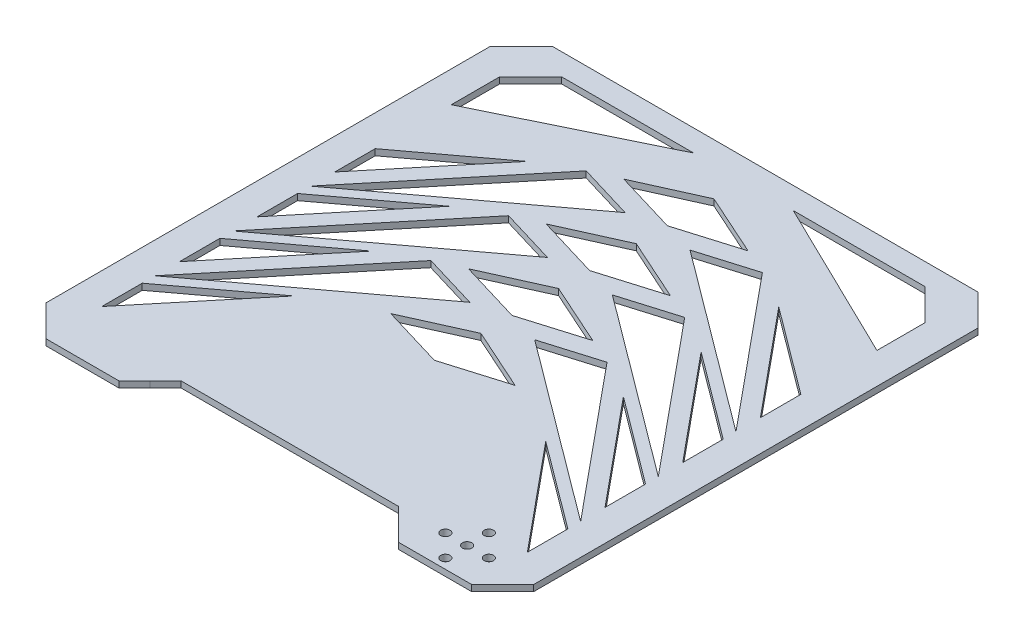
SolidWorks part; units mm, degrees
material "PE 低密度结膜"
ref_plane "前视基准面" through (0, 0, 0) normal (0, 0, 1) x (1, 0, 0)
ref_plane "上视基准面" through (0, 0, 0) normal (0, 1, 0) x (1, 0, 0)
ref_plane "右视基准面" through (0, 0, 0) normal (1, 0, 0) x (0, 0, -1)
sketch "草图1" plane through (0, 0, 0) normal (0, 1, 0) x (1, 0, 0)
  line L1 (-78.5, 81.5) -> (78.5, 81.5)
  line L2 (-78.5, 81.5) -> (-78.5, -81.5)
  line L3 (-78.5, -81.5) -> (78.5, -81.5)
  line L4 (78.5, 81.5) -> (78.5, -81.5)
  line L5 (-78.5, 81.5) -> (78.5, -81.5) construction
  line L6 (-78.5, -81.5) -> (78.5, 81.5) construction
  point P0 (0, 0)
  dimension "D1" = 163
  dimension "D2" = 157
extrude "凸台-拉伸1" add sketch "草图1" along normal blind 2
sketch "草图2" plane through (0, 0, 0) normal (0, -1, 0) x (-1, 0, 0)
  circle A0 centre (-56.9012, -78.3444) radius 1.5
  circle A1 centre (-63.9012, -71.3444) radius 1.5
  circle A2 centre (-56.9012, -64.3444) radius 1.5
  circle A3 centre (-49.9012, -71.3444) radius 1.5
  circle A4 centre (-56.9012, -71.3444) radius 1.5
  dimension "D1" = 3
  dimension "D2" = 3
  dimension "D3" = 3
  dimension "D4" = 3
extrude "切除-拉伸1" cut sketch "草图2" against normal blind 10
chamfer "Chamfer1" distance 10 angle 45 1 edges at (-78.5, 1, -81.5)
chamfer "Chamfer2" distance 10 angle 45 2 edges at (78.5, 1, 81.5) (-78.5, 1, 81.5)
chamfer "Chamfer3" distance 10 angle 45 1 edges at (78.5, 1, -81.5)
sketch "Sketch1" plane through (0, 2, 0) normal (0, 1, 0) x (1, 0, 0)
  line L0 (0, 0) -> (20, 6)
  line L1 (20, 6) -> (0, 15)
  line L2 (0, 15) -> (-20, 6)
  line L3 (-20, 6) -> (0, 0)
  line L4 (28.3522, 2.2415) -> (10.4403, -3.1321)
  line L5 (10.4403, -3.1321) -> (68.5, -46.4073)
  line L6 (68.5, -46.4073) -> (28.3522, 2.2415)
  line L7 (78.5, -71.5) -> (78.5, 71.5) construction
  line L8 (0, 81.5) -> (0, -81.5) construction
  line L9 (68.5, 81.5) -> (-68.5, 81.5) construction
  line L10 (-68.5, -81.5) -> (68.5, -81.5) construction
  line L11 (-68.5, -46.4073) -> (-28.3522, 2.2415)
  line L12 (-10.4403, -3.1321) -> (-68.5, -46.4073)
  line L13 (-28.3522, 2.2415) -> (-10.4403, -3.1321)
  line L17 (40.5567, -4.6917) -> (68.5, -25.5195)
  line L18 (68.5, -25.5195) -> (68.5, -38.5518)
  line L19 (40.5567, -4.6917) -> (68.5, -38.5518)
  line L20 (-68.5, -25.5195) -> (-68.5, -38.5518)
  line L21 (-40.5567, -4.6917) -> (-68.5, -38.5518)
  line L22 (-40.5567, -4.6917) -> (-68.5, -25.5195)
  dimension "D1" = 20
  dimension "D2" = 20
  dimension "D3" = 15
  dimension "D4" = 0
  dimension "D5" = 9
  dimension "D6" = 9
  dimension "D7" = 6
  dimension "D8" = 0
  dimension "D9" = 0
  dimension "D10" = 160
  dimension "D11" = 10
  dimension "D12" = 5
  dimension "D13" = 5
extrude "Cut-Extrude1" cut sketch "Sketch1" against normal blind 10
pattern_linear "LPattern1" count 3 spacing 25 along (0, 0, -1) of "Cut-Extrude1"
sketch "Sketch2" plane through (0, 0, 0) normal (0, -1, 0) x (1, 0, 0)
  line L0 (0, 0) -> (20, -6)
  line L1 (20, -6) -> (0, -15)
  line L2 (0, -15) -> (-20, -6)
  line L3 (-20, -6) -> (0, 0)
  line L4 (40.5567, 4.6917) -> (68.5, 38.5518)
  line L5 (68.5, 38.5518) -> (68.5, 25.5195)
  line L6 (68.5, 38.5518) -> (68.5, 25.5195) construction
  line L7 (68.5, 25.5195) -> (40.5567, 4.6917) construction
  line L8 (68.5, 25.5195) -> (40.5567, 4.6917)
  line L9 (-68.5, 38.5518) -> (-40.5567, 4.6917)
  line L10 (-40.5567, 4.6917) -> (-68.5, 25.5195) construction
  line L11 (-68.5, 38.5518) -> (-40.5567, 4.6917) construction
  line L12 (-40.5567, 4.6917) -> (-68.5, 25.5195)
  line L13 (-68.5, 25.5195) -> (-68.5, 38.5518)
pattern_linear "LPattern2" count 2 spacing 25 along (0, 0, 1) of "Cut-Extrude1"
sketch "Sketch3" plane through (0, 2, 0) normal (0, 1, 0) x (1, 0, 0)
  line L0 (-68.5, -71.4073) -> (-10.4403, -28.1321)
  line L1 (-10.4403, -28.1321) -> (-28.3522, -22.7585)
  line L2 (-28.3522, -22.7585) -> (-68.5, -71.4073)
  line L3 (10.4403, -28.1321) -> (28.3522, -22.7585)
  line L4 (28.3522, -22.7585) -> (68.5, -71.4073)
  line L5 (68.5, -71.4073) -> (10.4403, -28.1321)
  circle A0 centre (56.9012, -64.3444) radius 1.5
extrude "Boss-Extrude1" add sketch "Sketch3" against normal up to surface (2 mm away) contours L1 L2 L0 | A0 L5 L4 L3 region at (-35.7642, 2, 40.766) region at (35.7541, 2, 40.7556) up to face at (44.1913, 0, 50.2344)
sketch "Sketch4" plane through (0, 0, 0) normal (0, -1, 0) x (1, 0, 0)
  line L0 (-68.5, 81.5) -> (68.5, 81.5) construction
  line L1 (-40, 91.5) -> (40, 91.5)
  line L2 (-40, 91.5) -> (-40, 71.5)
  line L3 (-40, 71.5) -> (40, 71.5)
  line L4 (40, 91.5) -> (40, 71.5)
  line L5 (-40, 91.5) -> (40, 71.5) construction
  line L6 (-40, 71.5) -> (40, 91.5) construction
  point P0 (0, 81.5)
  dimension "D1" = 80
  dimension "D2" = 20
extrude "Cut-Extrude2" cut sketch "Sketch4" against normal blind 10
chamfer "Chamfer4" distance 5 angle 45 4 edges at (40, 1, 71.5) (40, 1, 81.5) (-40, 1, 71.5) (-40, 1, 81.5)
sketch "Sketch5" plane through (0, 2, 0) normal (0, 1, 0) x (1, 0, 0)
  line L0 (16.0408, 74.5) -> (68.5, 74.5)
  line L1 (68.5, 74.5) -> (68.5, 48.9712)
  line L2 (68.5, 48.9712) -> (16.0408, 74.5)
  line L3 (78.5, -71.5) -> (78.5, 71.5) construction
  line L4 (68.5, 81.5) -> (-68.5, 81.5) construction
  point P7 (5.3469, 74.5)
  point P8 (68.5, 53.8938)
  point P9 (11.6275, 74.5)
  point P10 (68.5, 48.9712)
  point P11 (16.0408, 74.5)
  point P12 (0, 0)
  dimension "D1" = 10
  dimension "D2" = 7
extrude "Cut-Extrude3" cut sketch "Sketch5" against normal blind 10
chamfer "Chamfer5" distance 10 angle 45 1 edges at (68.5, 1, -74.5)
mirror "Mirror1" about plane through (0, 0, 0) normal (1, 0, 0) of "Cut-Extrude3", "Chamfer5"
